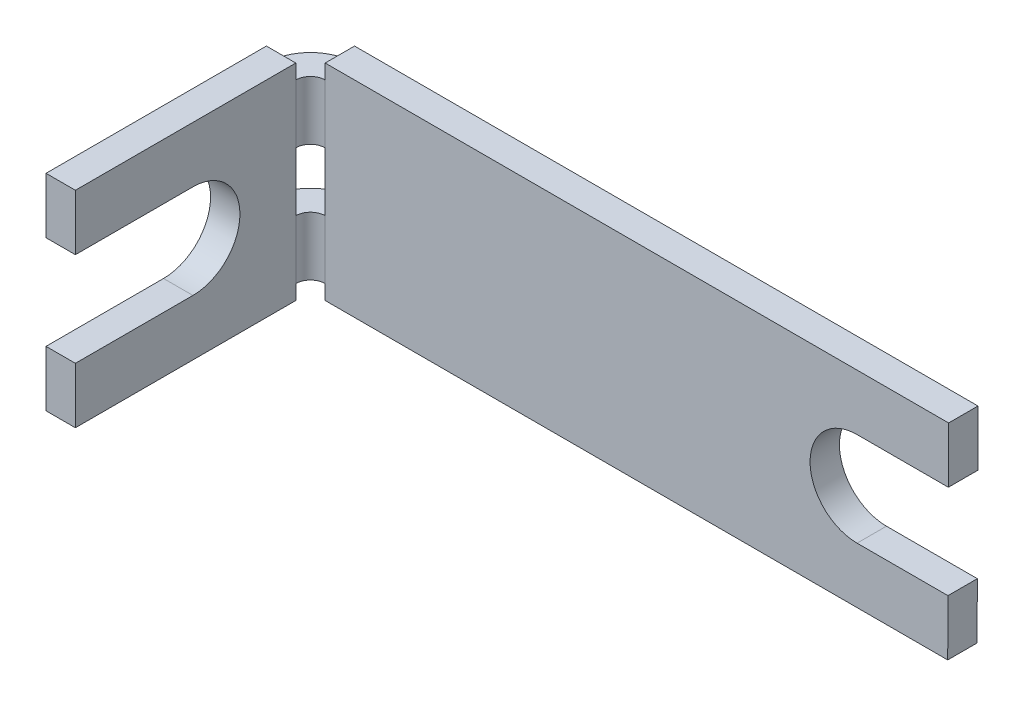
SolidWorks part; units mm, degrees
note: The reader was unsure of these and kept them because the rebuilt part matched: flange length of "Odgięcie krawędzi1".
ref_plane "Płaszczyzna przednia" through (0, 0, 0) normal (0, 0, 1) x (1, 0, 0)
ref_plane "Płaszczyzna górna" through (0, 0, 0) normal (0, 1, 0) x (1, 0, 0)
ref_plane "Płaszczyzna prawa" through (0, 0, 0) normal (1, 0, 0) x (0, 0, -1)
sketch "Szkic1" plane through (0, 0, 0) normal (0, 0, 1) x (1, 0, 0)
  line L0 (-5.8996, 4.5226) -> (-5.8996, -2.4774)
  line L1 (-5.8996, -2.4774) -> (15.785, -2.4774)
  line L2 (15.8075, 2.6226) -> (15.8159, 4.5226)
  line L3 (15.8159, 4.5226) -> (-5.8996, 4.5226)
  line L5 (13.6204, 2.6226) -> (15.8075, 2.6226)
  line L6 (13.6204, -0.5774) -> (15.7934, -0.5774)
  line L7 (13.6204, 1.0226) -> (5.0906, 1.0226) construction
  line L8 (13.6204, 2.6226) -> (12.7004, 2.6226)
  line L9 (13.6204, -0.5774) -> (12.7004, -0.5774)
  line L10 (15.785, -2.4774) -> (15.7934, -0.5774)
  arc A2 (12.7004, 2.6226) -> (12.7004, -0.5774) centre (12.7004, 1.0226) ccw
  dimension "D2" = 7
base flange "Odgięcie bazowe1" sketch "Szkic1" thickness 1 reverse thickness direction no parameters "D1"=0.5
edge flange "Odgięcie krawędzi1" sketch "Szkic4" flange angle 90 flange length 9 flange position material outside bend radius 0.5 thickness 1 relief rectangular parameters "D6"=10
sketch "Szkic4" plane through (-5.8996, 0, 0) normal (-1, 0, 0) x (0, -1, 0)
  line L0 (-4.5226, 0) -> (2.4774, 0) construction
  line L1 (-4.5226, 0) -> (2.4774, 0)
  line L2 (-4.5226, 0) -> (-4.5226, 8)
  line L3 (-4.5226, 8) -> (2.4774, 8)
  line L4 (2.4774, 8) -> (2.4774, 0)
bend "Zgięcie krawędziowe1" bend radius 0.5 bend angle 90 parameters "D5"=1
sketch "Szkic5" plane through (-6.8996, 0, 0) normal (-1, 0, 0) x (0, 0, 1)
  line L0 (8, 1.0226) -> (0.5, 1.0226) construction
  line L1 (8, -2.4774) -> (8, 4.5226) construction
  line L2 (0.5, -2.4774) -> (0.5, 4.5226) construction
  line L3 (4, -0.5774) -> (8, -0.5774)
  line L4 (4, 2.6226) -> (8, 2.6226)
  line L5 (8, 2.6226) -> (8, -0.5774)
  circle A0 centre (8, 1.0226) radius 4 construction
  arc A1 (4, 2.6226) -> (4, -0.5774) centre (4, 1.0226) ccw
extrude "Wytnij-wyciągnięcie1" cut sketch "Szkic5" against normal up to surface (1 mm away) normal cut yes up to face at (-5.8996, 1.0226, 4.25)
sketch "Szkic6" plane through (0, -2.4774, 0) normal (0, -1, 0) x (1, 0, 0)
  line L0 (-5.8996, 0.5) -> (-5.3996, 0)
  line L1 (-5.3996, 0) -> (-5.3996, -1)
  line L2 (-5.3996, -1) -> (-6.8996, -1)
  line L3 (-5.8996, 0.5) -> (-6.8996, 0.5)
  line L4 (-6.8996, 0.5) -> (-6.8996, -1)
sketch "Szkic7" plane through (0, 4.5226, 0) normal (0, 1, 0) x (1, 0, 0)
  line L0 (-6.8996, -0.5) -> (-6.8996, 1)
  line L1 (-5.3996, 1) -> (-6.8996, 1)
  line L2 (-6.8996, -0.5) -> (-5.3996, -0.5)
  line L3 (-5.3996, 1) -> (-5.3996, -0.5)
sketch "Szkic8" plane through (-6.8996, 0, 0) normal (-1, 0, 0) x (0, 0, 1)
  line L1 (-4.1974, 2.0226) -> (-4.1974, 0.0226)
  line L3 (0.5, 2.0226) -> (0.5, 0.0226)
  line L5 (0.5, 2.0226) -> (-4.1974, 2.0226)
  line L6 (0.5, 0.0226) -> (-4.1974, 0.0226)
ref_plane "Płaszczyzna1" through (-5.3996, 0, 0) normal (1, 0, 0) x (0, 0, -1)
extrude "Wytnij-wyciągnięcie2" cut sketch "Szkic8" against normal up to surface (1.5 mm away) normal cut yes up to plane "Płaszczyzna1"
extrude "Wytnij-wyciągnięcie5" cut sketch "Szkic6" against normal blind 0.5 normal cut yes
extrude "Wytnij-wyciągnięcie6" cut sketch "Szkic7" against normal blind 0.5 normal cut yes
sketch "Linie zgięcia1" [suppressed] plane through (0, 0, 0) normal (0, 1, 0) x (1, 0, 0)
sketch "Ramka-graniczna1" [suppressed] plane through (0, 0, 0) normal (0, 1, 0) x (1, 0, 0)
sheet metal parameters "Arkusz blachy1" thickness 1 parameters "D1"=0.7366
flat pattern "Rozłożony model1" [suppressed]
sketch "Linie zgięcia2" plane through (0, 0, 0) normal (0, 1, 0) x (1, 0, 0)
sketch3d "Ramka-graniczna2" [suppressed]
  line L0 (-19.52, -3.5, 0) -> (3.5, -3.5, 0) construction
  line L1 (-19.52, 3.5, 0) -> (3.5, 3.5, 0) construction
  line L2 (-19.52, -3.5, 0) -> (-19.52, 3.5, 0) construction
  line L3 (3.5, -3.5, 0) -> (3.5, 3.5, 0) construction
sheet metal parameters "Arkusz blachy2" thickness 1 parameters "D1"=0.7366
flat pattern "Rozłożony model1"
sketch "Linie zgięcia2" plane through (0, 0, 0) normal (0, 0, 1) x (1, 0, 0)
  line L0 (-6.185, 4.5226) -> (-6.185, -2.4774) construction
  line L1 (-6.185, 4.5226) -> (-6.185, -2.4774) construction
sketch3d "Ramka-graniczna2" [suppressed]
  line L0 (-28.0908, -3.5, 0) -> (3.5, -3.5, 0) construction
  line L1 (-28.0908, 3.5, 0) -> (3.5, 3.5, 0) construction
  line L2 (-28.0908, -3.5, 0) -> (-28.0908, 3.5, 0) construction
  line L3 (3.5, -3.5, 0) -> (3.5, 3.5, 0) construction
bend of the flat pattern "Rozłożone-<Zgięcie krawędziowe1>1"
sheet metal parameters "Arkusz blachy3" thickness 1 parameters "D1"=0.7366
flat pattern "Rozłożony model1"
sketch "Linie zgięcia2" plane through (0, 0, 0) normal (0, 0, 1) x (1, 0, 0)
  line L0 (-6.185, 4.5226) -> (-6.185, -2.4774) construction
  line L1 (-6.185, 4.5226) -> (-6.185, -2.4774) construction
sketch3d "Ramka-graniczna2" [suppressed]
  line L0 (-27.1708, 3.5, 0) -> (3.1155, 3.5, 0) construction
  line L1 (-27.1708, -3.5, 0) -> (3.1155, -3.5, 0) construction
  line L2 (-27.1708, 3.5, 0) -> (-27.1708, -3.5, 0) construction
  line L3 (3.1155, 3.5, 0) -> (3.1155, -3.5, 0) construction
bend of the flat pattern "Rozłożone-<Zgięcie krawędziowe1>1"
sheet metal parameters "Arkusz blachy6" thickness 1 parameters "D1"=0.7366
flat pattern "Rozłożony model1"
sketch "Linie zgięcia2" plane through (0, 0, 0) normal (0, 0, 1) x (1, 0, 0)
  line L0 (-6.185, -0.5774) -> (-6.185, -2.4774) construction
  line L1 (-6.185, -0.5774) -> (-6.185, -2.4774) construction
  line L2 (-6.185, 4.5226) -> (-6.185, 2.6226) construction
sketch3d "Ramka-graniczna2" [suppressed]
  line L0 (-27.1708, 3.5, 0) -> (3.1155, 3.5, 0) construction
  line L1 (-27.1708, -3.5, 0) -> (3.1155, -3.5, 0) construction
  line L2 (-27.1708, 3.5, 0) -> (-27.1708, -3.5, 0) construction
  line L3 (3.1155, 3.5, 0) -> (3.1155, -3.5, 0) construction
bend of the flat pattern "Rozłożone-<Zgięcie krawędziowe1>1"
sheet metal parameters "Arkusz blachy11" thickness 1 parameters "D1"=0.7366
flat pattern "Rozłożony model1"
sketch "Linie zgięcia2" plane through (0, 0, 0) normal (0, 0, 1) x (1, 0, 0)
  line L0 (-6.185, -0.5774) -> (-6.185, -1.9774) construction
  line L1 (-6.185, -0.5774) -> (-6.185, -1.9774) construction
  line L2 (-6.185, 4.5226) -> (-6.185, 2.6226) construction
sketch3d "Ramka-graniczna2" [suppressed]
  line L0 (-27.1708, 3.5, 0) -> (3.1155, 3.5, 0) construction
  line L1 (-27.1708, -3.5, 0) -> (3.1155, -3.5, 0) construction
  line L2 (-27.1708, 3.5, 0) -> (-27.1708, -3.5, 0) construction
  line L3 (3.1155, 3.5, 0) -> (3.1155, -3.5, 0) construction
bend of the flat pattern "Rozłożone-<Zgięcie krawędziowe1>1"
sheet metal parameters "Arkusz blachy12" thickness 1 parameters "D1"=0.7366
flat pattern "Rozłożony model1"
sketch "Linie zgięcia2" plane through (0, 0, 0) normal (0, 0, 1) x (1, 0, 0)
  line L0 (-6.185, 0.0226) -> (-6.185, -1.9774) construction
  line L1 (-6.185, 0.0226) -> (-6.185, -1.9774) construction
  line L2 (-6.185, 4.0226) -> (-6.185, 2.0226) construction
sketch3d "Ramka-graniczna2" [suppressed]
  line L0 (-27.1708, 3.5, 0) -> (3.1155, 3.5, 0) construction
  line L1 (-27.1708, -3.5, 0) -> (3.1155, -3.5, 0) construction
  line L2 (-27.1708, 3.5, 0) -> (-27.1708, -3.5, 0) construction
  line L3 (3.1155, 3.5, 0) -> (3.1155, -3.5, 0) construction
bend of the flat pattern "Rozłożone-<Zgięcie krawędziowe1>1"
